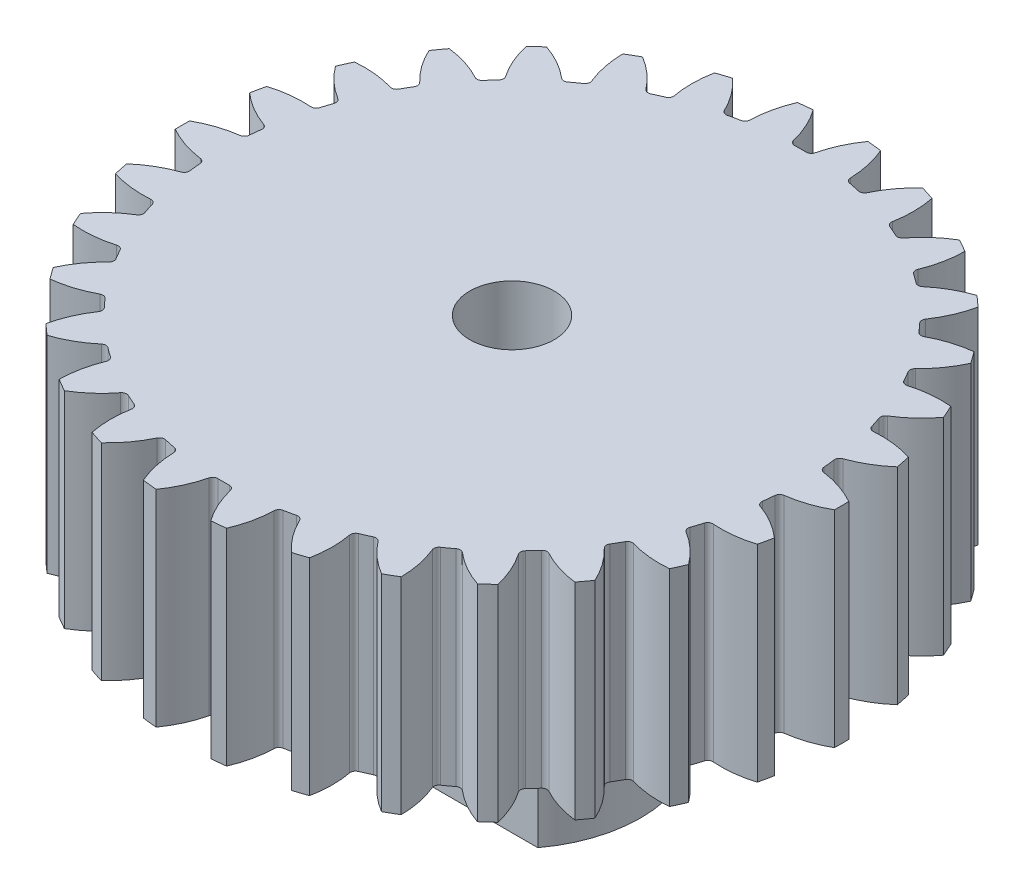
SolidWorks part; units mm, degrees
material "聚脂树脂"
ref_plane "前视基准面" through (0, 0, 0) normal (0, 0, 1) x (1, 0, 0)
ref_plane "上视基准面" through (0, 0, 0) normal (0, 1, 0) x (1, 0, 0)
ref_plane "右视基准面" through (0, 0, 0) normal (1, 0, 0) x (0, 0, -1)
other "Configuration Table"
sketch "草图1" plane through (0, 0, 0) normal (0, 1, 0) x (1, 0, 0)
  circle A0 centre (0, 0) radius 32
  dimension "D1" = 64
extrude "凸台-拉伸1" add sketch "草图1" along normal blind 20
sketch "草图2" plane through (0, 0, 0) normal (0, 1, 0) x (1, 0, 0)
  circle A0 centre (0, 0) radius 12.5
  dimension "D1" = 25
extrude "凸台-拉伸2" add sketch "草图2" against normal blind 16
sketch "草图4" plane through (0, 0, 0) normal (0, 1, 0) x (1, 0, 0)
  line L0 (0, 56.0311) -> (0, -31.5538) construction
  line L1 (0, 0) -> (2.9102, 55.5305) construction
  line L2 (1.5701, 29.9589) -> (26.7103, 28.6413) construction
  line L3 (1.5701, 29.9589) -> (25.2198, 19.9202) construction
  line L4 (11.015, 25.9497) -> (0, 0) construction
  circle A0 centre (0, 0) radius 30 construction
  arc A2 (2.6489, 31.8902) -> (1.0455, 28.3763) centre (11.015, 25.9497) ccw
  arc A8 (2.6489, 31.8902) -> (-2.6489, 31.8902) centre (0, 0) ccw
  circle A9 centre (0, 0) radius 32 construction
  arc A15 (0.5498, 27.9946) -> (-0.5498, 27.9946) centre (0, 0) ccw
  arc A16 (1.0455, 28.3763) -> (0.5498, 27.9946) centre (0.5596, 28.4945) cw
  arc A17 (-1.0455, 28.3763) -> (-0.5498, 27.9946) centre (-0.5596, 28.4945) ccw
  arc A18 (-2.6489, 31.8902) -> (-1.0455, 28.3763) centre (-11.015, 25.9497) cw
  dimension "D1" = 60
  dimension "D4" = 28
  dimension "D5" = 0.5
  dimension "D2" = 3
  dimension "D3" = 20
extrude "切除-拉伸1" cut sketch "草图4" along normal up to next
pattern_circular "阵列(圆周)1" count 30 over 360 about axis through (0, 20, 0) along (0, 1, 0) of "切除-拉伸1"
sketch "草图7" plane through (0, 0, 0) normal (0, 0, 1) x (1, 0, 0)
  line L0 (0, 37.4487) -> (0, -32.2732) construction
  line L2 (-12.5, -16) -> (12.5, -16) construction
  circle A2 centre (5.5, -8) radius 1.7
  circle A3 centre (-5.5, -8) radius 1.7
  dimension "D1" = 3.4
  dimension "D2" = 8
  dimension "D3" = 5.5
  dimension "D4" = 5.5
extrude "切除-拉伸4" cut sketch "草图7" against normal through all both and the other way through all
sketch "草图6" plane through (0, 0, 0) normal (0, 1, 0) x (1, 0, 0)
  circle A0 centre (0, 0) radius 30 construction
  dimension "D1" = 60
sketch "草图8" plane through (0, 0, 0) normal (0, 0, 1) x (1, 0, 0)
  line L0 (-12.5, -16) -> (12.5, -16) construction
  line L1 (-12.5, -16) -> (12.5, -16)
  line L2 (-12.5, -16) -> (-12.5, 0)
  line L3 (-12.5, 0) -> (12.5, 0)
  line L4 (12.5, -16) -> (12.5, 0)
  line L5 (30, 0) -> (-30, 0) construction
  line L6 (0, -17.9573) -> (0, 22.5638) construction
  dimension "D1" = 25
sketch "草图5" plane through (0, 0, 0) normal (0, 1, 0) x (1, 0, 0)
  circle A0 centre (0, 0) radius 4.1
  dimension "D1" = 8.2
extrude "切除-拉伸2" cut sketch "草图5" against normal through all both and the other way through all
extrude "切除-拉伸5" cut sketch "草图8" along normal blind 5 from offset 12.5 offset against normal yes
extrude "切除-拉伸6" cut sketch "草图8<2>" against normal blind 5 from offset 12.5
sketch "草图8<2>" plane through (0, 0, 0) normal (0, 0, 1) x (1, 0, 0) same geometry as "草图8"
sketch "草图9" plane through (0, 20, 0) normal (0, 1, 0) x (1, 0, 0)
  line L0 (3.7642, 1.625) -> (5.4, 1.625)
  line L1 (5.4, 1.625) -> (5.4, -1.625)
  line L2 (5.4, -1.625) -> (3.7642, -1.625)
  line L3 (5.4, 0) -> (0, 0) construction
  circle A0 centre (0, 0) radius 4.1 construction
  arc A1 (3.7642, 1.625) -> (3.7642, -1.625) centre (0, 0) ccw
  circle A2 centre (0, 0) radius 4.65 construction
  dimension "D1" = 9.3
  dimension "D2" = 5.4
  dimension "D3" = 3.25
extrude "切除-拉伸7" cut sketch "草图9" along normal blind 15 from surface starting at face at (0, -16, 4.1)
